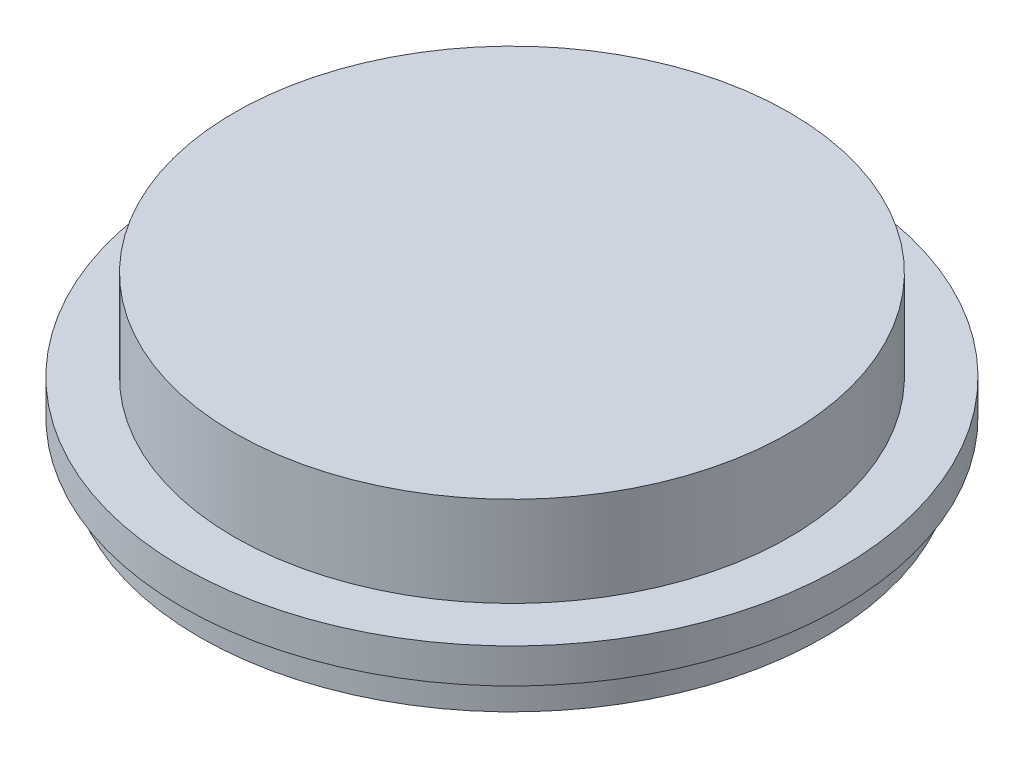
SolidWorks part; units mm, degrees
material "Epoxy, Unfilled"
ref_plane "Front Plane" through (0, 0, 0) normal (0, 0, 1) x (1, 0, 0)
ref_plane "Top Plane" through (0, 0, 0) normal (0, 1, 0) x (1, 0, 0)
ref_plane "Right Plane" through (0, 0, 0) normal (1, 0, 0) x (0, 0, -1)
sketch "Sketch1" plane through (0, 0, 0) normal (0, 0, 1) x (1, 0, 0)
  line L0 (0, 3.81) -> (0, -12.7) construction
  line L1 (60.325, 0) -> (60.325, -6.35)
  line L2 (60.325, -6.35) -> (57.15, -6.35)
  line L3 (57.15, -6.35) -> (57.15, -12.7)
  line L4 (57.15, -12.7) -> (50.8, -12.7)
  line L5 (50.8, -12.7) -> (50.8, -6.35)
  line L10 (60.325, 0) -> (50.8, 0)
  line L11 (50.8, 0) -> (50.8, 16.51)
  line L12 (50.8, 16.51) -> (0, 16.51)
  line L13 (0, 16.51) -> (0, 10.16)
  line L14 (0, 10.16) -> (44.45, 10.16)
  line L15 (44.45, 10.16) -> (44.45, -6.35)
  line L16 (44.45, -6.35) -> (50.8, -6.35)
  dimension "D1" = 60.325
  dimension "D2" = 3.175
  dimension "D3" = 6.35
  dimension "D4" = 6.35
  dimension "D5" = 6.35
revolve "Revolve1" add sketch "Sketch1" angle 360 about L0 region at (59.6548, -3.175, 0)
